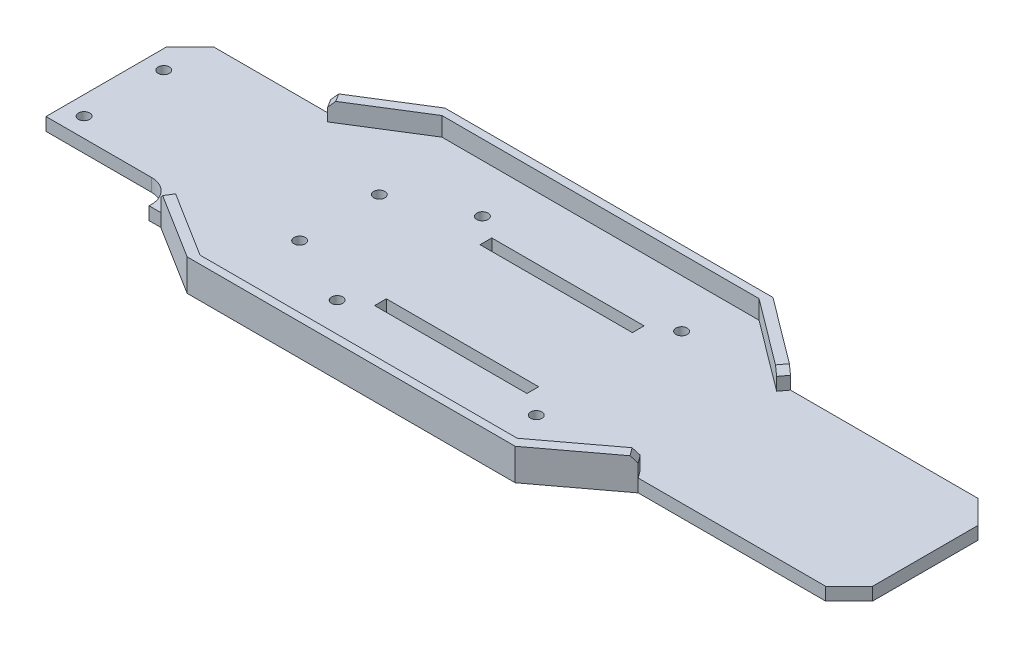
SolidWorks part; units mm, degrees
material "PETG - Polymaker"
ref_plane "Front Plane" through (0, 0, 0) normal (0, 0, 1) x (1, 0, 0)
ref_plane "Top Plane" through (0, 0, 0) normal (0, 1, 0) x (1, 0, 0)
ref_plane "Right Plane" through (0, 0, 0) normal (1, 0, 0) x (0, 0, -1)
sketch "Sketch1" plane through (0, 0, 0) normal (0, 1, 0) x (1, 0, 0)
  line L0 (-235.1499, 0) -> (235.1499, 0) construction
  line L1 (0, 0) -> (0, 52596.8311) construction
  line L2 (-100, 36.25) -> (-70, 55)
  line L3 (-70, 55) -> (70, 55)
  line L4 (-100, 36.25) -> (-160, 36.25)
  line L5 (-160, 36.25) -> (-160, -36.25)
  line L6 (-70, -55) -> (70, -55)
  line L7 (-100, -36.25) -> (-70, -55)
  line L8 (-100, -36.25) -> (-160, -36.25)
  line L9 (70, 55) -> (100, 32.5)
  line L10 (100, 32.5) -> (190, 32.5)
  line L11 (190, 32.5) -> (190, -32.5)
  line L12 (100, -32.5) -> (190, -32.5)
  line L13 (70, -55) -> (100, -32.5)
  point P3 (0, 0)
  point P10 (-85, 45.625)
  point P15 (-85, -45.625)
  point P18 (-160, 0)
  point P19 (0, -55)
  point P20 (0, 55)
  point P23 (190, 0)
  dimension "D1" = 55
  dimension "D2" = 72.5
  dimension "D3" = 30
  dimension "D4" = 60
  dimension "D5" = 140
  dimension "D6" = 90
  dimension "D7" = 65
  dimension "D8" = 30
  dimension "D9" = 110
extrude "Boss-Extrude1" add sketch "Sketch1" along normal blind 5.5
sketch "Sketch3" plane through (0, 5.5, 0) normal (0, 1, 0) x (1, 0, 0)
  line L0 (0, 0) -> (50000, 0) construction
  line L1 (0, 0) -> (0, 50000) construction
  line L2 (0, 55) -> (-70, 55)
  line L3 (70, 55) -> (-70, 55) construction
  line L4 (-70, 55) -> (-100, 36.25)
  line L5 (-100, 36.25) -> (-97.88, 32.858)
  line L6 (-97.88, 32.858) -> (-67.88, 51.608)
  line L7 (-67.88, 51.608) -> (0, 51.608)
  line L8 (-70, 55) -> (-67.88, 51.608) construction
  line L9 (0, 55) -> (70, 55)
  line L10 (70, 55) -> (100, 32.5)
  line L11 (100, 32.5) -> (97.456, 29.108)
  line L12 (97.456, 29.108) -> (67.456, 51.608)
  line L13 (67.456, 51.608) -> (0, 51.608)
  line L14 (67.456, 51.608) -> (70, 55) construction
  line L15 (67.456, -51.608) -> (70, -55) construction
  line L16 (-70, -55) -> (-67.88, -51.608) construction
  line L17 (67.456, -51.608) -> (0, -51.608)
  line L18 (97.456, -29.108) -> (67.456, -51.608)
  line L19 (100, -32.5) -> (97.456, -29.108)
  line L20 (70, -55) -> (100, -32.5)
  line L21 (0, -55) -> (70, -55)
  line L22 (-67.88, -51.608) -> (0, -51.608)
  line L23 (-97.88, -32.858) -> (-67.88, -51.608)
  line L24 (-100, -36.25) -> (-97.88, -32.858)
  line L25 (-70, -55) -> (-100, -36.25)
  line L26 (0, -55) -> (-70, -55)
  dimension "D1" = 4
extrude "Chassis-Walls1" add sketch "Sketch3" along normal blind 8
chamfer "Chamfer1" distance 10 angle 45 2 edges at (-160, 2.75, -36.25) (-160, 2.75, 36.25)
chamfer "Chamfer2" distance 10 angle 45 2 edges at (190, 2.75, -32.5) (190, 2.75, 32.5)
chamfer "Chamfer3" distance 2.5 angle 45 4 edges at (-98.94, 13.5, -34.554) (-98.94, 13.5, 34.554) (98.728, 13.5, 30.804) (98.728, 13.5, -30.804)
sketch "Sketch4" plane through (0, 0, 0) normal (0, -1, 0) x (1, 0, 0)
  line L0 (0, 0) -> (50000, 0) construction
  line L1 (-152, 17) -> (-60, 17) construction
  line L2 (-160, -26.25) -> (-160, 26.25) construction
  circle A0 centre (-152, 17) radius 2.4
  circle A1 centre (-60, 17) radius 2.4
  circle A2 centre (-60, -17) radius 2.4
  circle A3 centre (-152, -17) radius 2.4
  circle A4 centre (-30, 31) radius 2.4
  circle A5 centre (55, 31) radius 2.4
  circle A6 centre (55, -31) radius 2.4
  circle A7 centre (-30, -31) radius 2.4
  dimension "D1" = 4.8
  dimension "D2" = 4.8
  dimension "D6" = 4.8
  dimension "D8" = 4.8
  dimension "D3" = 8
  dimension "D4" = 92
  dimension "D5" = 34
  dimension "D7" = 30
  dimension "D9" = 85
  dimension "D10" = 62
extrude "Cut-Extrude1" cut sketch "Sketch4" against normal blind 10
sketch "Sketch5" plane through (0, 5.5, 0) normal (0, 1, 0) x (1, 0, 0)
  line L0 (-160, -25.25) -> (-105, -25.25)
  line L1 (-160, 26.25) -> (-160, -26.25) construction
  line L2 (-105, -25.25) -> (-105, -36.25)
  line L3 (-150, -36.25) -> (-100, -36.25) construction
  line L4 (-105, -36.25) -> (-160, -36.25)
  line L5 (-160, -36.25) -> (-160, -25.25)
  dimension "D1" = 55
  dimension "D2" = 11
extrude "Cut-Extrude2" cut sketch "Sketch5" against normal blind 10
sketch "Sketch6" plane through (0, 5.5, 0) normal (0, 1, 0) x (1, 0, 0)
  line L0 (0, 0) -> (50000, 0) construction
  line L1 (55, 31) -> (-30, 31) construction
  line L2 (12.5, 30.75) -> (12.5, 50030.75) construction
  line L3 (-20, -20) -> (45, -25) construction
  line L4 (-20, 25) -> (45, 25)
  line L5 (-20, 25) -> (-20, 20)
  line L6 (-20, 20) -> (45, 20)
  line L7 (45, 25) -> (45, 20)
  line L8 (-20, 25) -> (45, 20) construction
  line L9 (-20, 20) -> (45, 25) construction
  line L10 (-20, -25) -> (45, -20) construction
  line L11 (45, -25) -> (45, -20)
  line L12 (-20, -20) -> (45, -20)
  line L13 (-20, -25) -> (-20, -20)
  line L14 (-20, -25) -> (45, -25)
  point P9 (12.5, 31)
  point P10 (12.5, 22.5)
  point P19 (12.5, -22.5)
  dimension "D1" = 5
  dimension "D2" = 65
  dimension "D3" = 20
extrude "Cut-Extrude3" cut sketch "Sketch6" against normal through all
fillet "Fillet1" radius 10 1 edges at (-105, 2.75, 25.25)
equation "\"D6@Sketch4\"=\"D2@Sketch4\""
equation "\"D8@Sketch4\"=\"D2@Sketch4\""
